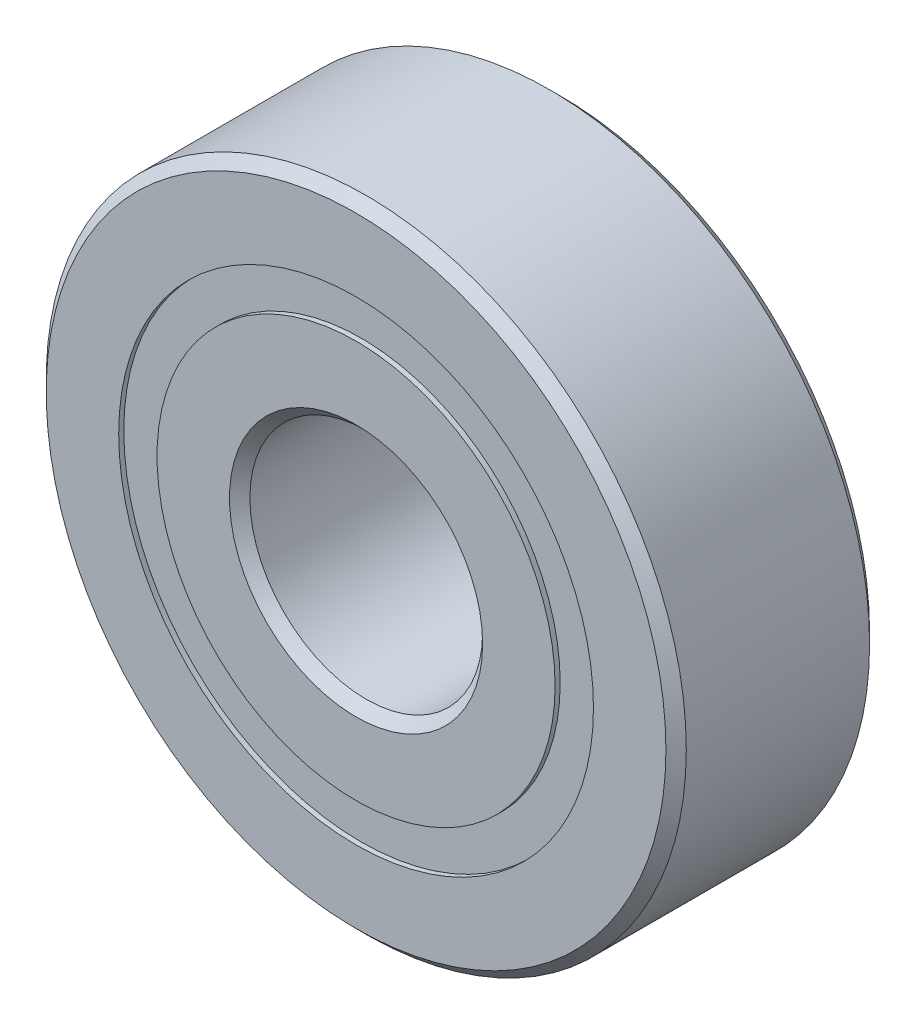
SolidWorks part; units mm, degrees
material "AISI 316 Annealed Stainless Steel Bar (SS)"
ref_plane "Front Plane" through (0, 0, 0) normal (0, 0, 1) x (1, 0, 0)
ref_plane "Top Plane" through (0, 0, 0) normal (0, 1, 0) x (1, 0, 0)
ref_plane "Right Plane" through (0, 0, 0) normal (1, 0, 0) x (0, 0, -1)
sketch "Sketch1" plane through (0, 0, 0) normal (1, 0, 0) x (0, 0, -1)
  line L0 (-3.5, 0) -> (3.5, 0) construction
  line L1 (0, 11) -> (0, -11) construction
  line L2 (3.15, 11) -> (-3.15, 11)
  line L3 (-3.15, 11) -> (-3.5, 10.65)
  line L4 (-3.5, 10.65) -> (-3.5, 8.1593)
  line L5 (-3.5, 8.1593) -> (-1.5556, 8.1593)
  line L6 (3.5, 8.1593) -> (1.5556, 8.1593)
  line L7 (3.5, 10.65) -> (3.5, 8.1593)
  line L8 (3.15, 11) -> (3.5, 10.65)
  line L9 (0, 11) -> (0, 7.5) construction
  line L10 (0, 7.5) -> (0, 4) construction
  arc A0 (-1.5556, 8.1593) -> (1.5556, 8.1593) centre (0, 7.5) cw
  point P14 (0, 4)
  dimension "Width" = 7
  dimension "OD" = 22
  dimension "D1" = 45
  dimension "D2" = 0.35
  dimension "Shaft Dia" = 8
  dimension "D3" = 3.1111
  dimension "D4" = 0.6593
revolve "Revolve1" add sketch "Sketch1" angle 360 about L0
sketch "Sketch3" plane through (0, 0, 0) normal (1, 0, 0) x (0, 0, -1)
  line L0 (-3.5, 6.8407) -> (-1.5556, 6.8407)
  line L1 (0, 11) -> (0, -11) construction
  line L2 (-3.5, 10.65) -> (-3.5, 8.1593) construction
  line L3 (-3.5, 6.8407) -> (-3.5, 4.35)
  line L4 (-3.15, 11) -> (-3.5, 10.65) construction
  line L5 (-3.5, 4.35) -> (-3.15, 4)
  line L6 (-3.15, 4) -> (3.15, 4)
  line L7 (3.15, 11) -> (3.15, -11) construction
  line L8 (3.15, 4) -> (3.5, 4.35)
  line L9 (3.5, -10.65) -> (3.5, 10.65) construction
  line L10 (3.5, 4.35) -> (3.5, 6.8407)
  line L11 (3.5, 6.8407) -> (1.5556, 6.8407)
  line L13 (3.15, 11) -> (3.5, 10.65) construction
  arc A0 (1.5556, 8.1593) -> (-1.5556, 8.1593) centre (0, 7.5) ccw construction
  arc A1 (1.5556, 6.8407) -> (-1.5556, 6.8407) centre (0, 7.5) cw
revolve "Revolve3" add sketch "Sketch3" angle 360 about L0
sketch "Sketch4" plane through (0, 0, 0) normal (1, 0, 0) x (0, 0, -1)
  line L0 (-1.6895, 7.5) -> (1.6895, 7.5)
  arc A2 (-1.6895, 7.5) -> (1.6895, 7.5) centre (0, 7.5) cw
  arc A3 (1.5556, 8.1593) -> (-1.5556, 8.1593) centre (0, 7.5) ccw construction
revolve "Revolve4" add sketch "Sketch4" angle 360 about L0
ref_axis "Axis1" through (0, 0, -3.5) along (0, 0, 1)
pattern_circular "CirPattern1" [suppressed] count 10 every 36 about axis through (0, 0, -3.5) along (0, 0, 1) of bodies 104
sketch "Sketch6" plane through (0, 0, 0) normal (1, 0, 0) x (0, 0, -1)
  line L0 (-3.5, 8.1593) -> (-1.5556, 8.1593) construction
  line L1 (-3.325, 8.1593) -> (-1.6895, 8.1593)
  line L2 (-3.325, 8.1593) -> (-3.325, 6.8407)
  line L3 (-3.325, 6.8407) -> (-1.6895, 6.8407)
  line L4 (-1.6895, 8.1593) -> (-1.6895, 6.8407)
  line L5 (-3.5, 6.8407) -> (-1.5556, 6.8407) construction
  line L6 (3.5, 8.1593) -> (1.5556, 8.1593) construction
  line L7 (3.325, 8.1593) -> (1.6895, 8.1593)
  line L8 (3.325, 8.1593) -> (3.325, 6.8407)
  line L9 (3.325, 6.8407) -> (1.6895, 6.8407)
  line L10 (1.6895, 8.1593) -> (1.6895, 6.8407)
  line L11 (3.5, 6.8407) -> (1.5556, 6.8407) construction
  line L12 (-3.15, 11) -> (-3.5, 10.65) construction
  point P18 (-3.325, 10.825)
revolve "Revolve5" add sketch "Sketch6" angle 360 about L0
equation "\"D2@Sketch1\" = \"Width@Sketch1\"*.05"
equation "\"D3@Sketch1\" = \"Width@Sketch1\"/2.25"
equation "\"D4@Sketch1\" = (((\"OD@Sketch1\"-\"Width@Sketch1\")/2)/3.25)/3.5"
equation "\"D2@CirPattern1\" = 360/\"Balls@CirPattern1\""
